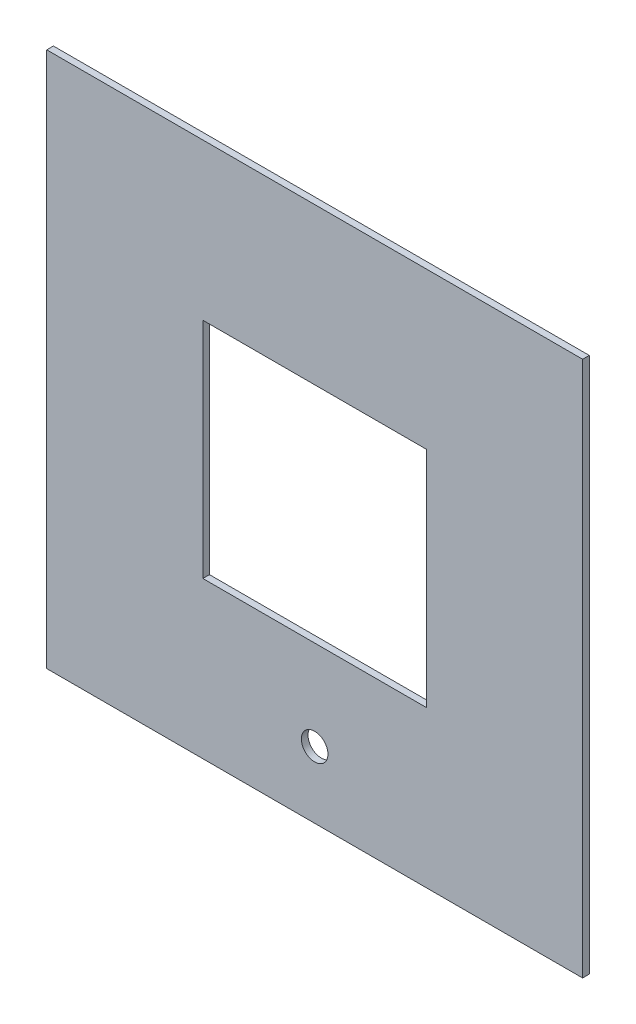
SolidWorks part; units mm, degrees
ref_plane "Alzado" through (0, 0, 0) normal (0, 0, 1) x (1, 0, 0)
ref_plane "Planta" through (0, 0, 0) normal (0, 1, 0) x (1, 0, 0)
ref_plane "Vista lateral" through (0, 0, 0) normal (1, 0, 0) x (0, 0, -1)
sketch "Sketch1" plane through (0, 0, 0) normal (0, 0, 1) x (1, 0, 0)
  line L1 (-121, 121) -> (121, 121)
  line L2 (-121, 121) -> (-121, -121)
  line L3 (-121, -121) -> (121, -121)
  line L4 (121, 121) -> (121, -121)
  line L5 (-121, 121) -> (121, -121) construction
  line L6 (-121, -121) -> (121, 121) construction
  line L7 (-50.5, 50.5) -> (50.5, 50.5)
  line L8 (-50.5, 50.5) -> (-50.5, -50.5)
  line L9 (-50.5, -50.5) -> (50.5, -50.5)
  line L10 (50.5, 50.5) -> (50.5, -50.5)
  line L11 (-50.5, 50.5) -> (50.5, -50.5) construction
  line L12 (-50.5, -50.5) -> (50.5, 50.5) construction
  point P0 (0, 0)
  point P6 (0, 0)
  dimension "D1" = 242
  dimension "D2" = 242
  dimension "D3" = 101
extrude "Boss-Extrude1" add sketch "Sketch1" along normal blind 3
sketch "Sketch2" plane through (0, 0, 3) normal (0, 0, 1) x (1, 0, 0)
  circle A0 centre (0, -91) radius 6
  dimension "D1" = 12
extrude "Cut-Extrude1" cut sketch "Sketch2" against normal up to next
